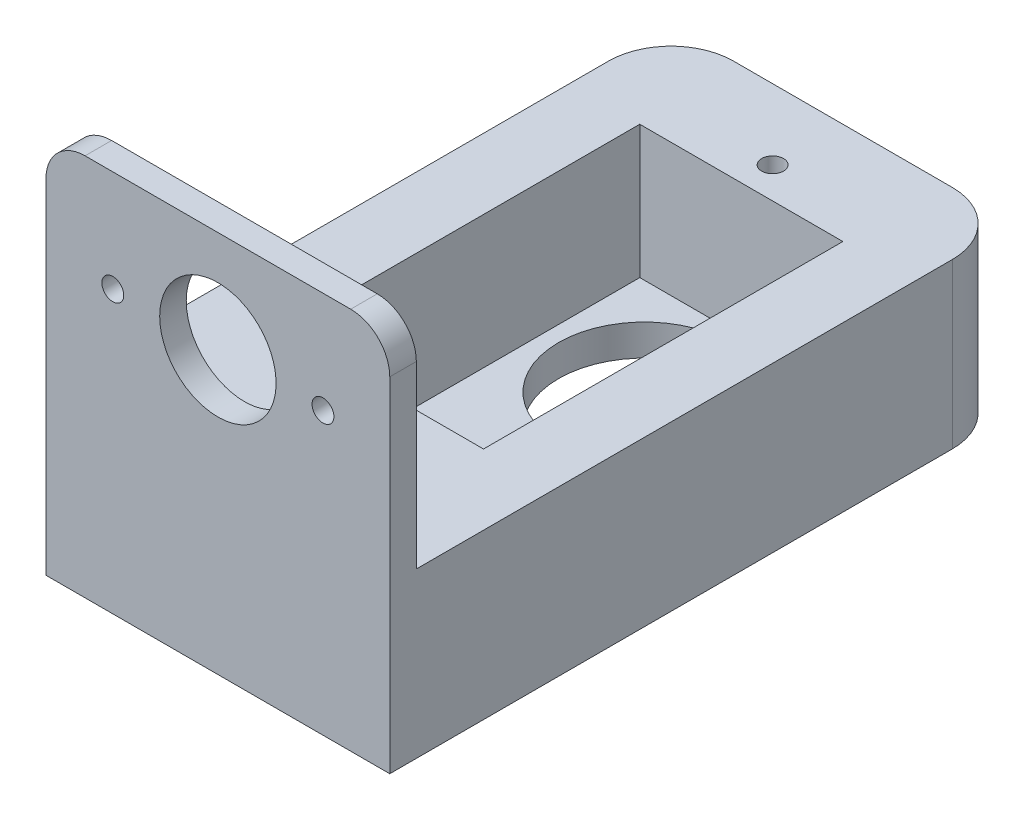
SolidWorks part; units mm, degrees
ref_plane "Front Plane" through (0, 0, 0) normal (0, 0, 1) x (1, 0, 0)
ref_plane "Top Plane" through (0, 0, 0) normal (0, 1, 0) x (1, 0, 0)
ref_plane "Right Plane" through (0, 0, 0) normal (1, 0, 0) x (0, 0, -1)
sketch "Sketch1" plane through (0, 0, 0) normal (0, 1, 0) x (1, 0, 0)
  line L1 (0, 0) -> (22, 0)
  line L2 (0, 0) -> (0, 40)
  line L3 (0, 40) -> (22, 40)
  line L4 (22, 0) -> (22, 40)
  dimension "D1" = 22
  dimension "D2" = 40
extrude "Boss-Extrude1" add sketch "Sketch1" along normal blind 10.5 contours L2 L3 L4 L1
sketch "Sketch2" plane through (0, 10.5, 0) normal (0, 1, 0) x (1, 0, 0)
  line L0 (0, 0) -> (0, 40) construction
  line L1 (4.5, 33.5) -> (17.5, 33.5)
  line L2 (4.5, 33.5) -> (4.5, 10.5)
  line L3 (4.5, 10.5) -> (17.5, 10.5)
  line L4 (17.5, 33.5) -> (17.5, 10.5)
  line L5 (0, 0) -> (22, 0) construction
  dimension "D1" = 13
  dimension "D2" = 23
  dimension "D3" = 4.5
  dimension "D4" = 10.5
extrude "Cut-Extrude1" cut sketch "Sketch2" against normal blind 8.5
sketch "Sketch3" plane through (0, 2, 0) normal (0, 1, 0) x (1, 0, 0)
  line L0 (17.5, 33.5) -> (4.5, 33.5) construction
  line L1 (17.5, 10.5) -> (17.5, 33.5) construction
  circle A0 centre (11, 27.3) radius 5.5
  dimension "D1" = 6.2
  dimension "D2" = 6.5
extrude "Cut-Extrude2" cut sketch "Sketch3" against normal through all
sketch "Sketch4" plane through (0, 10.5, 0) normal (0, 1, 0) x (1, 0, 0)
  line L0 (0, 0) -> (0, 40) construction
  line L1 (0, 1.7) -> (22, 1.7)
  line L2 (0, 1.7) -> (0, 0)
  line L3 (0, 0) -> (22, 0)
  line L4 (22, 1.7) -> (22, 0)
  dimension "D1" = 1.7
extrude "Boss-Extrude2" add sketch "Sketch4" along normal blind 14
sketch "Sketch5" plane through (0, 0, -1.7) normal (0, 0, -1) x (-1, 0, 0)
  line L0 (-22, 24.5) -> (-22, 10.5) construction
  line L1 (-22, 10.5) -> (0, 10.5) construction
  circle A0 centre (-11, 18) radius 3.725
  circle A3 centre (-17.725, 18) radius 0.7
  circle A4 centre (-4.275, 18) radius 0.7
  dimension "D1" = 7.45
  dimension "D2" = 3
  dimension "D5" = 7.5
  dimension "D3" = 3
  dimension "D4" = 11
extrude "Cut-Extrude3" cut sketch "Sketch5" against normal through all contours A0
extrude "Cut-Extrude4" cut sketch "Sketch5<3>" against normal blind 10
sketch "Sketch5<3>" plane through (0, 0, -1.7) normal (0, 0, -1) x (-1, 0, 0) same geometry as "Sketch5"
sketch "Sketch6" plane through (0, 10.5, 0) normal (0, 1, 0) x (1, 0, 0)
  line L0 (17.5, 33.5) -> (4.5, 33.5) construction
  line L1 (4.5, 10.5) -> (17.5, 10.5) construction
  circle A0 centre (11, 35.5) radius 0.7
  circle A1 centre (11, 7.5) radius 0.7
  dimension "D1" = 2
  dimension "D2" = 1.4
  dimension "D3" = 3
extrude "Cut-Extrude5" cut sketch "Sketch6" against normal blind 2.5
fillet "Fillet1" radius 4 2 edges at (0, 5.25, -40) (22, 5.25, -40)
fillet "Fillet2" radius 2.5 2 edges at (0, 24.5, -0.85) (22, 24.5, -0.85)
